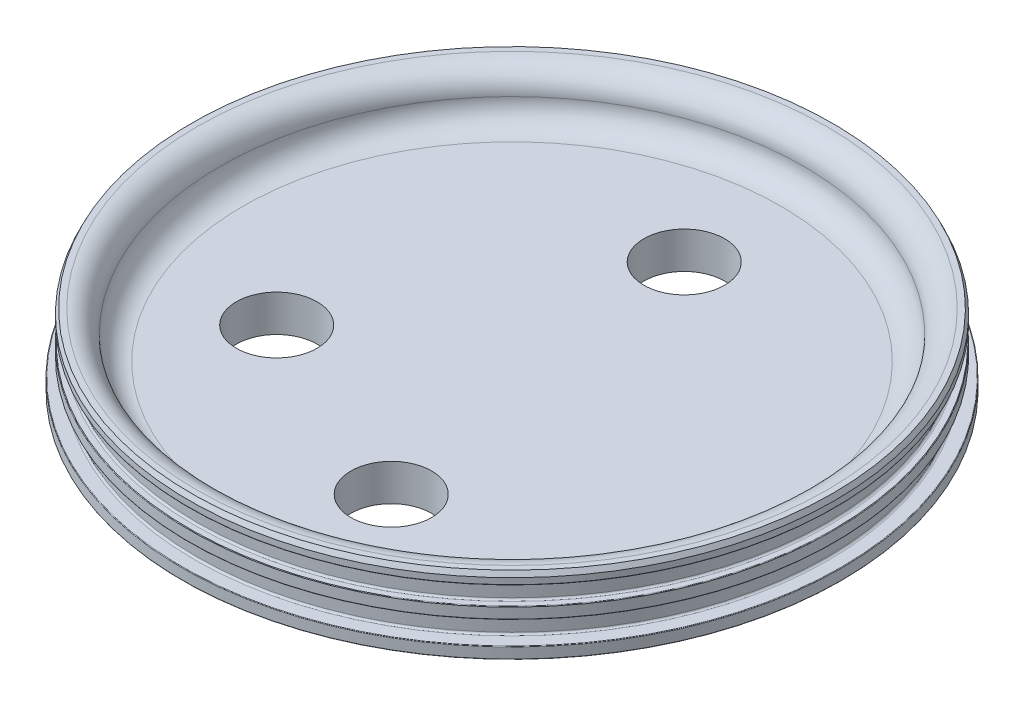
SolidWorks part; units mm, degrees
material "6061-T6 (SS)"
ref_plane "Front Plane" through (0, 0, 0) normal (0, 0, 1) x (1, 0, 0)
ref_plane "Top Plane" through (0, 0, 0) normal (0, 1, 0) x (1, 0, 0)
ref_plane "Right Plane" through (0, 0, 0) normal (1, 0, 0) x (0, 0, -1)
sketch "Sketch1" plane through (0, 0, 0) normal (0, 0, 1) x (1, 0, 0)
  line L0 (0, 48.1922) -> (0, -25.6743) construction
  line L1 (0, 0) -> (72.898, 0)
  line L2 (72.898, 0) -> (72.898, 2.54)
  line L3 (72.898, 2.54) -> (69.6468, 2.54)
  line L4 (69.6468, 2.54) -> (69.6468, 6.604)
  line L5 (69.6468, 6.604) -> (71.4248, 6.604)
  line L6 (71.4248, 6.604) -> (71.4248, 9.144)
  line L7 (71.4248, 9.144) -> (69.6468, 9.144)
  line L8 (64.5668, 15.748) -> (64.5668, 5.588)
  line L9 (64.5668, 5.588) -> (0, 5.588)
  line L10 (0, 5.588) -> (0, 0)
  line L11 (69.6468, 9.144) -> (69.6468, 13.208)
  line L12 (69.6468, 13.208) -> (71.4248, 13.208)
  line L13 (71.4248, 13.208) -> (71.4248, 15.748)
  line L14 (71.4248, 15.748) -> (64.5668, 15.748)
  dimension "D2" = 4.064
  dimension "D5" = 5.588
  dimension "D7" = 4.064
  dimension "D3" = 2.54
  dimension "D4" = 2.54
  dimension "D8" = 5.08
  dimension "D9" = 10.16
  dimension "D1" = 72.898
  dimension "D10" = 1.778
  dimension "D6" = 69.6468
revolve "Revolve1" add sketch "Sketch1" angle 360 about L0
sketch "Sketch6" plane through (0, 0, 0) normal (0, -1, 0) x (1, 0, 0)
  circle A0 centre (0, 0) radius 66.04
  dimension "D1" = 132.08
extrude "Boss-Extrude1" add sketch "Sketch6" along normal blind 2.54
fillet "CNC ID Fillet" radius 0.4064 5 edges at (-69.6468, 6.604, 0) (-69.6468, 2.54, 0) (66.04, 0, 0) (-69.6468, 13.208, 0) (-69.6468, 9.144, 0)
fillet "CNC OD Fillet" radius 0.127 6 edges at (-71.4248, 6.604, 0) (-72.898, 2.54, 0) (-71.4248, 9.144, 0) (-71.4248, 13.208, 0) (66.04, -2.54, 0) (-72.898, 0, 0)
chamfer "CNC Chamfers" distance 0.508 angle 65 1 edges at (-71.4248, 15.748, 0) first distance on face at (-64.5668, 15.748, 0)
hole_wizard "Pipe Tap Drill for 1/2 Tap - Fill Valve" positions "Sketch13" profile "Sketch14" hole size "1/2" standard "ANSI Inch" end condition through all
sketch "Sketch13" plane through (0, -2.54, 0) normal (0, -1, 0) x (-1, 0, 0)
  point P4 (0, 38.1)
  dimension "D1" = 38.1
sketch "Sketch14" plane through (0, -2.54, -38.1) normal (1, 0, 0) x (0, 0, -1)
  line L0 (0, 0) -> (0, 18.288)
  line L1 (0, 18.288) -> (8.9281, 18.288)
  line L2 (8.9281, 18.288) -> (8.9281, 0)
  line L5 (8.9281, 0) -> (0, 0)
  line L11 (0, -6.35) -> (0, 107.95) construction
  dimension "Thru Hole Dia." = 17.8562
  dimension "Thru Hole Depth" = 18.288
hole_wizard "Pipe Tap Drill for 1/4 Tap - Solenoid Valve" positions "Sketch15" profile "Sketch16" hole size "1/2" standard "ANSI Inch" end condition through all
sketch "Sketch15" plane through (0, -2.54, 0) normal (0, -1, 0) x (-1, 0, 0)
  line L2 (-12.0892, -38.8003) -> (0, 0) construction
  line L3 (0, 0) -> (0, -38.8003) construction
  point P4 (-12.0892, -38.8003)
  dimension "D1" = 17.306
  dimension "D2" = 40.64
  dimension "D3" = 38.8003
sketch "Sketch16" plane through (12.0892, -2.54, 38.8003) normal (1, 0, 0) x (0, 0, -1)
  line L0 (0, 0) -> (0, 18.288)
  line L1 (0, 18.288) -> (8.9281, 18.288)
  line L2 (8.9281, 18.288) -> (8.9281, 0)
  line L5 (8.9281, 0) -> (0, 0)
  line L11 (0, -6.35) -> (0, 107.95) construction
  dimension "Thru Hole Dia." = 17.8562
  dimension "Thru Hole Depth" = 18.288
hole_wizard "Pipe Tap Drill for 1/2 Tap - Cryo Valve" positions "Sketch17" profile "Sketch18" hole size "1/2" standard "ANSI Inch" end condition through all
sketch "Sketch17" plane through (0, -2.54, 0) normal (0, -1, 0) x (-1, 0, 0)
  line L0 (32.9956, -19.05) -> (17.2813, -19.05) construction
  line L2 (32.9956, -19.05) -> (0, 0) construction
  point P4 (32.9956, -19.05)
  dimension "D1" = 30
  dimension "D2" = 38.1
sketch "Sketch18" plane through (-32.9956, -2.54, 19.05) normal (1, 0, 0) x (0, 0, -1)
  line L0 (0, 0) -> (0, 18.288)
  line L1 (0, 18.288) -> (8.9281, 18.288)
  line L2 (8.9281, 18.288) -> (8.9281, 0)
  line L5 (8.9281, 0) -> (0, 0)
  line L11 (0, -6.35) -> (0, 107.95) construction
  dimension "Thru Hole Dia." = 17.8562
  dimension "Thru Hole Depth" = 18.288
fillet "Fillet1" radius 5.08 2 edges at (-64.5668, 5.588, 0) (-64.5668, 15.748, 0)
equation "\"D6@Sketch1\"=5.484/2"
